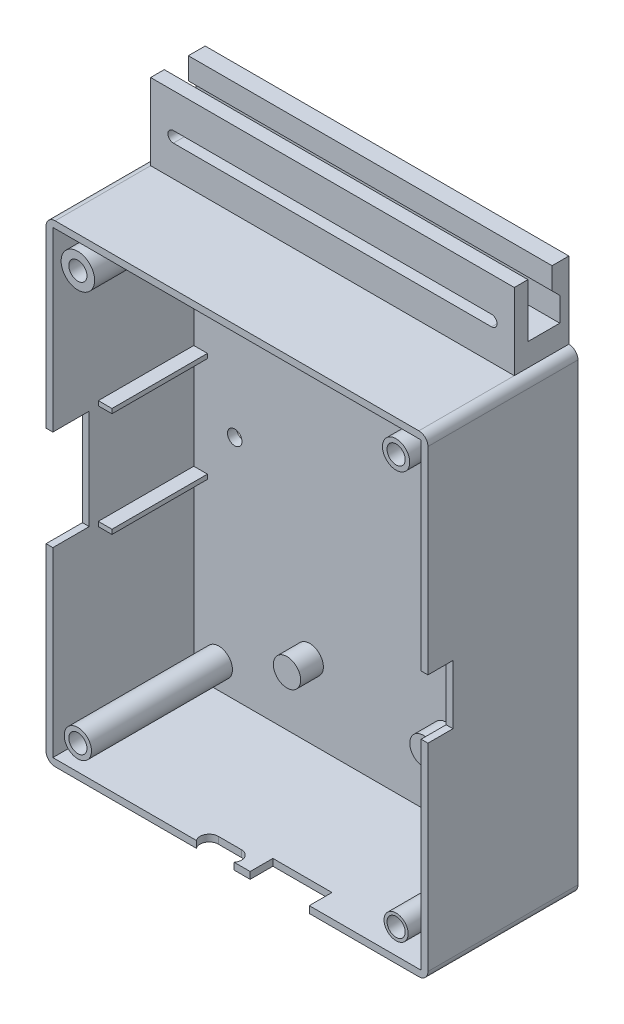
SolidWorks part; units mm, degrees
ref_plane "前视基准面" through (0, 0, 0) normal (0, 0, 1) x (1, 0, 0)
ref_plane "上视基准面" through (0, 0, 0) normal (0, 1, 0) x (1, 0, 0)
ref_plane "右视基准面" through (0, 0, 0) normal (1, 0, 0) x (0, 0, -1)
sketch "草图1" plane through (0, 0, 0) normal (0, 0, 1) x (1, 0, 0)
  line L0 (-1, 50) -> (-1, 40)
  line L1 (40, 50) -> (19, 50)
  line L2 (40, 50) -> (40, -50)
  line L3 (40, -50) -> (-40, -50)
  line L4 (-40, 50) -> (-40, -50)
  line L5 (40, 50) -> (-40, -50) construction
  line L6 (40, -50) -> (-40, 50) construction
  line L7 (-1, 40) -> (19, 40)
  line L8 (19, 40) -> (19, 50)
  line L9 (-1, 50) -> (-40, 50)
  circle A0 centre (-21.79, 39.3) radius 1.6
  circle A1 centre (21.79, 39.3) radius 1.6
  circle A2 centre (-21.79, -39.3) radius 1.6
  circle A3 centre (21.79, -39.3) radius 1.6
  circle A4 centre (-35, 45) radius 1.6
  circle A5 centre (35, 45) radius 1.6
  circle A6 centre (35, -45) radius 1.6
  circle A7 centre (-35, -45) radius 1.6
  point P0 (0, 0)
  dimension "D7" = 3.2
  dimension "D8" = 3.2
  dimension "D13" = 3.2
  dimension "D14" = 3.2
  dimension "D15" = 3.2
  dimension "D16" = 3.2
  dimension "D17" = 3.2
  dimension "D18" = 3.2
  dimension "D1" = 100
  dimension "D2" = 80
  dimension "D3" = 5
  dimension "D4" = 5
  dimension "D5" = 5
  dimension "D6" = 5
  dimension "D9" = 5
  dimension "D10" = 5
  dimension "D11" = 5
  dimension "D12" = 5
  dimension "D19" = 18.21
  dimension "D20" = 10.7
  dimension "D21" = 10.7
  dimension "D22" = 18.21
  dimension "D23" = 18.21
  dimension "D24" = 18.21
  dimension "D25" = 10.7
  dimension "D26" = 10.7
  dimension "D27" = 39
  dimension "D28" = 59
  dimension "D29" = 10
sketch "草图2" plane through (0, 0, 0) normal (0, 0, 1) x (1, 0, 0)
  circle A0 centre (-35, 45) radius 2
  circle A1 centre (35, 45) radius 2
  circle A2 centre (-35, -45) radius 2
  circle A3 centre (35, -45) radius 2
  circle A4 centre (35, 45) radius 3
  circle A5 centre (-35, 45) radius 3.6869
  circle A6 centre (35, -45) radius 2.65
  circle A7 centre (-35, -45) radius 3
  dimension "D1" = 4
  dimension "D2" = 4
  dimension "D3" = 4
  dimension "D4" = 4
  dimension "D5" = 6
  dimension "D6" = 6
  dimension "D7" = 5.3
extrude "凸台-拉伸1" add sketch "草图2" against normal blind 31
sketch "草图3" plane through (0, 0, -31) normal (0, 0, -1) x (-1, 0, 0)
  line L0 (-40, 50) -> (-40, -50) construction
  line L1 (-40.5, 50.5) -> (40.5, 50.5)
  line L2 (-40.5, 50.5) -> (-40.5, -50.5)
  line L3 (-40.5, -50.5) -> (40.5, -50.5)
  line L4 (40.5, 50.5) -> (40.5, -50.5)
  line L5 (-40.5, 50.5) -> (40.5, -50.5) construction
  line L6 (-40.5, -50.5) -> (40.5, 50.5) construction
  line L7 (-40, 50) -> (-19, 50) construction
  line L9 (-40, -52) -> (40, -52)
  line L10 (-42, -50) -> (-42, 50)
  line L11 (-40, 52) -> (40, 52)
  line L12 (42, -50) -> (42, 50)
  line L13 (-42, -52) -> (42, 52) construction
  line L14 (-42, 52) -> (42, -52) construction
  arc A0 (-40, 52) -> (-42, 50) centre (-40, 50) ccw
  arc A2 (-42, -50) -> (-40, -52) centre (-40, -50) ccw
  arc A4 (42, 50) -> (40, 52) centre (40, 50) ccw
  arc A5 (40, -52) -> (42, -50) centre (40, -50) ccw
  point P0 (0, 0)
  point P10 (0, 0)
  dimension "D5" = 4
  dimension "D7" = 4
  dimension "D1" = 0.5
  dimension "D2" = 0.5
  dimension "D3" = 1.5
  dimension "D4" = 1.5
extrude "凸台-拉伸2" add sketch "草图3" against normal blind 31 separate body
sketch "草图4" plane through (0, 0, -31) normal (0, 0, -1) x (-1, 0, 0)
  line L4 (40, 52) -> (-40, 52)
  line L5 (-42, 50) -> (-42, -50)
  line L6 (-40, -52) -> (40, -52)
  line L7 (42, -50) -> (42, 50)
  line L8 (40, 52) -> (-40, 52)
  line L9 (-42, 50) -> (-42, -50)
  line L10 (-40, -52) -> (40, -52)
  line L11 (42, -50) -> (42, 50)
  arc A4 (42, 50) -> (40, 52) centre (40, 50) ccw
  arc A5 (-40, 52) -> (-42, 50) centre (-40, 50) ccw
  arc A6 (-42, -50) -> (-40, -52) centre (-40, -50) ccw
  arc A7 (40, -52) -> (42, -50) centre (40, -50) ccw
  arc A8 (42, 50) -> (40, 52) centre (40, 50) ccw
  arc A9 (-40, 52) -> (-42, 50) centre (-40, 50) ccw
  arc A10 (-42, -50) -> (-40, -52) centre (-40, -50) ccw
  arc A11 (40, -52) -> (42, -50) centre (40, -50) ccw
  dimension "D1" = 0
extrude "凸台-拉伸3" add sketch "草图4" along normal blind 2
sketch "草图5" plane through (-42, 0, 0) normal (-1, 0, 0) x (0, 0, 1)
  line L1 (0, 11.5) -> (-8, 11.5)
  line L2 (0, 11.5) -> (0, -10.5)
  line L3 (0, -10.5) -> (-8, -10.5)
  line L4 (-8, 11.5) -> (-8, -10.5)
  line L5 (-33, 50) -> (0, 50) construction
  line L6 (-33, -50) -> (0, -50) construction
  line L7 (0, -50) -> (0, 50) construction
  dimension "D1" = 38.5
  dimension "D2" = 39.5
  dimension "D3" = 8
extrude "切除-拉伸1" cut sketch "草图5" against normal up to next
sketch "草图6" plane through (42, 0, 0) normal (1, 0, 0) x (0, 0, -1)
  line L1 (0, 6.5) -> (5.5, 6.5)
  line L2 (0, 6.5) -> (0, -6.5)
  line L3 (0, -6.5) -> (5.5, -6.5)
  line L4 (5.5, 6.5) -> (5.5, -6.5)
  line L5 (33, 50) -> (0, 50) construction
  line L6 (33, -50) -> (0, -50) construction
  line L7 (0, 50) -> (0, -50) construction
  dimension "D1" = 43.5
  dimension "D2" = 43.5
  dimension "D3" = 5.5
extrude "切除-拉伸2" cut sketch "草图6" against normal up to next
sketch "草图7" plane through (0, -52, 0) normal (0, -1, 0) x (1, 0, 0)
  line L0 (-2.213, -1.2) -> (-7.313, -1.2) construction
  line L1 (-2.213, -3.2) -> (-7.313, -3.2)
  line L2 (-2.213, 0.8) -> (-7.313, 0.8)
  line L3 (-40, -33) -> (-40, 0) construction
  line L4 (40, 0) -> (-40, 0) construction
  line L6 (2.897, 0) -> (15.897, 0)
  line L7 (2.897, 0) -> (2.897, -5)
  line L8 (2.897, -5) -> (15.897, -5)
  line L9 (15.897, 0) -> (15.897, -5)
  line L10 (-40.5, 0) -> (40.5, 0) construction
  arc A0 (-2.213, -3.2) -> (-2.213, 0.8) centre (-2.213, -1.2) ccw
  arc A1 (-7.313, 0.8) -> (-7.313, -3.2) centre (-7.313, -1.2) ccw
  point P2 (-4.763, -1.2)
  point P7 (-9.313, -1.2)
  dimension "D2" = 37.787
  dimension "D3" = 2
  dimension "D1" = 30.687
  dimension "D4" = 3.2
  dimension "D5" = 42.897
  dimension "D6" = 55.897
  dimension "D7" = 5
extrude "切除-拉伸3" cut sketch "草图7" against normal up to next
sketch "草图8" plane through (0, 0, -31) normal (0, 0, 1) x (1, 0, 0)
  line L1 (-8.913, -52) -> (-40, -52) construction
  line L2 (40, -52) -> (15.897, -52) construction
  circle A0 centre (-15, -34.5) radius 3
  circle A1 centre (15, -34.5) radius 3
  circle A2 centre (-10, 46) radius 3
  circle A3 centre (10, 46) radius 3
  circle A4 centre (-10, 30) radius 3
  circle A5 centre (10, 30) radius 3
  dimension "D3" = 6
  dimension "D4" = 6
  dimension "D7" = 6
  dimension "D8" = 6
  dimension "D9" = 6
  dimension "D10" = 6
  dimension "D2" = 17.5
  dimension "D5" = 30
  dimension "D6" = 15
  dimension "D11" = 10
  dimension "D12" = 20
  dimension "D13" = 16
  dimension "D14" = 30
  dimension "D15" = 17.5
extrude "凸台-拉伸4" add sketch "草图8" along normal blind 5
sketch "草图9" plane through (0, 0, -33) normal (0, 0, -1) x (-1, 0, 0)
  line L4 (40, 52) -> (-40, 52)
  line L5 (-42, 50) -> (-42, -50)
  line L6 (-40, -52) -> (40, -52)
  line L7 (42, -50) -> (42, 50)
  line L8 (40, 52) -> (-40, 52)
  line L9 (-42, 50) -> (-42, -50)
  line L10 (-40, -52) -> (40, -52)
  line L11 (42, -50) -> (42, 50)
  circle A0 centre (10, 46) radius 3 construction
  circle A1 centre (-10, 46) radius 3 construction
  arc A4 (42, 50) -> (40, 52) centre (40, 50) ccw
  arc A5 (-40, 52) -> (-42, 50) centre (-40, 50) ccw
  arc A6 (-42, -50) -> (-40, -52) centre (-40, -50) ccw
  arc A7 (40, -52) -> (42, -50) centre (40, -50) ccw
  arc A8 (42, 50) -> (40, 52) centre (40, 50) ccw
  arc A9 (-40, 52) -> (-42, 50) centre (-40, 50) ccw
  arc A10 (-42, -50) -> (-40, -52) centre (-40, -50) ccw
  arc A11 (40, -52) -> (42, -50) centre (40, -50) ccw
  circle A12 centre (-15, -34.5) radius 2
  circle A13 centre (15, -34.5) radius 2
  circle A14 centre (10, 30) radius 3 construction
  circle A15 centre (-10, 30) radius 3 construction
  circle A22 centre (-10, 46) radius 2
  circle A23 centre (10, 46) radius 2
  circle A24 centre (10, 30) radius 2
  circle A25 centre (-10, 30) radius 2
  point P21 (0, 0)
  dimension "D2" = 4
  dimension "D3" = 4
  dimension "D4" = 4
  dimension "D5" = 4
  dimension "D6" = 4
  dimension "D7" = 4
  dimension "D8" = 17.5
  dimension "D9" = 17.5
  dimension "D1" = 0
extrude "切除-拉伸4" cut sketch "草图9" against normal blind 5 contours A12 | A13 | A22 | A23 | A24 | A25 region at (15, -34.5, -33) region at (-15, -34.5, -33)
sketch "草图10" plane through (0, 52, 0) normal (0, 1, 0) x (1, 0, 0)
  line L0 (-40, 33) -> (-40, 0) construction
  line L1 (40, 33) -> (-40, 33)
  line L2 (40, 33) -> (40, 21)
  line L3 (40, 21) -> (-40, 21)
  line L4 (-40, 33) -> (-40, 21)
  dimension "D1" = 12
extrude "凸台-拉伸5" add sketch "草图10" along normal blind 5
sketch "草图11" plane through (-40, 0, 0) normal (-1, 0, 0) x (0, 0, 1)
  line L0 (-33, 57) -> (-33, 68.8)
  line L1 (-33, 68.8) -> (-29.3, 68.8)
  line L2 (-29.3, 68.8) -> (-29.3, 64)
  line L3 (-29.3, 64) -> (-31, 62.3)
  line L4 (-31, 62.3) -> (-31, 57)
  line L5 (-33, 57) -> (-21, 57) construction
  line L7 (-24, 57) -> (-24, 68.8)
  line L8 (-24, 68.8) -> (-21, 68.8)
  line L9 (-21, 68.8) -> (-21, 57)
  line L10 (-21, 57) -> (-24, 57)
  line L11 (-33, 57) -> (-31, 57)
  dimension "D1" = 7
  dimension "D2" = 2
  dimension "D3" = 5.3
  dimension "D4" = 1.7
  dimension "D5" = 1.7
  dimension "D6" = 4.8
  dimension "D7" = 11.8
  dimension "D8" = 11.8
extrude "凸台-拉伸6" add sketch "草图11" against normal up to surface (80 mm away) up to face at (40, 54.5, -27)
sketch "草图12" plane through (0, 0, -24) normal (0, 0, -1) x (-1, 0, 0)
  line L0 (-35, 60) -> (35, 60) construction
  line L1 (-35, 61.2) -> (35, 61.2)
  line L2 (-35, 58.8) -> (35, 58.8)
  line L3 (-40, 57) -> (40, 57) construction
  arc A0 (-35, 61.2) -> (-35, 58.8) centre (-35, 60) ccw
  arc A1 (35, 58.8) -> (35, 61.2) centre (35, 60) ccw
  point P2 (0, 60)
  dimension "D2" = 1.2
  dimension "D1" = 3
  dimension "D3" = 35
extrude "切除-拉伸5" cut sketch "草图12" against normal up to surface (3 mm away) up to face at (0, 60.4, -21)
sketch "草图13" plane through (0, 0, -31) normal (0, 0, 1) x (1, 0, 0)
  line L0 (-40.5, 50.5) -> (40.5, 50.5) construction
  circle A0 centre (-31.5, -0.5) radius 1.6
  circle A1 centre (31.5, -0.5) radius 1.6
  dimension "D1" = 3.2
  dimension "D2" = 3.2
  dimension "D3" = 51
  dimension "D4" = 51
  dimension "D5" = 63
  dimension "D6" = 31.5
extrude "切除-拉伸6" cut sketch "草图13" against normal through all
sketch "草图14" plane through (-40.5, 0, 0) normal (1, 0, 0) x (0, 0, -1)
  line L0 (8, -10.5) -> (8, 11.5) construction
  line L1 (10, 11.5) -> (31, 11.5)
  line L2 (10, 11.5) -> (10, 12.5)
  line L3 (10, 12.5) -> (31, 12.5)
  line L4 (31, 11.5) -> (31, 12.5)
  line L6 (31, -50.5) -> (31, 50.5) construction
  line L7 (8, 11.5) -> (0, 11.5) construction
  line L8 (0, -10.5) -> (8, -10.5) construction
  line L9 (10, -10.5) -> (31, -10.5)
  line L10 (10, -10.5) -> (10, -11.5)
  line L11 (10, -11.5) -> (31, -11.5)
  line L12 (31, -10.5) -> (31, -11.5)
  dimension "D1" = 2
  dimension "D2" = 1
  dimension "D3" = 1
  dimension "D4" = 2
extrude "凸台-拉伸7" add sketch "草图14" along normal blind 3
sketch "草图15" plane through (40.5, 0, 0) normal (-1, 0, 0) x (0, 0, 1)
  line L0 (-8, 11.5) -> (-8, -10.5) construction
  line L1 (-10, 11.5) -> (-31, 11.5)
  line L2 (-10, 11.5) -> (-10, 12.5)
  line L3 (-10, 12.5) -> (-31, 12.5)
  line L4 (-31, 11.5) -> (-31, 12.5)
  line L5 (-10, -10.5) -> (-31, -10.5)
  line L6 (-10, -10.5) -> (-10, -11.5)
  line L7 (-10, -11.5) -> (-31, -11.5)
  line L8 (-31, -10.5) -> (-31, -11.5)
  line L9 (0, 11.5) -> (-8, 11.5) construction
  line L10 (-8, -10.5) -> (0, -10.5) construction
  line L11 (-31, 50.5) -> (-31, -50.5) construction
  dimension "D1" = 2
  dimension "D2" = 2
  dimension "D3" = 1
  dimension "D4" = 1
extrude "凸台-拉伸8" add sketch "草图15" along normal blind 3
